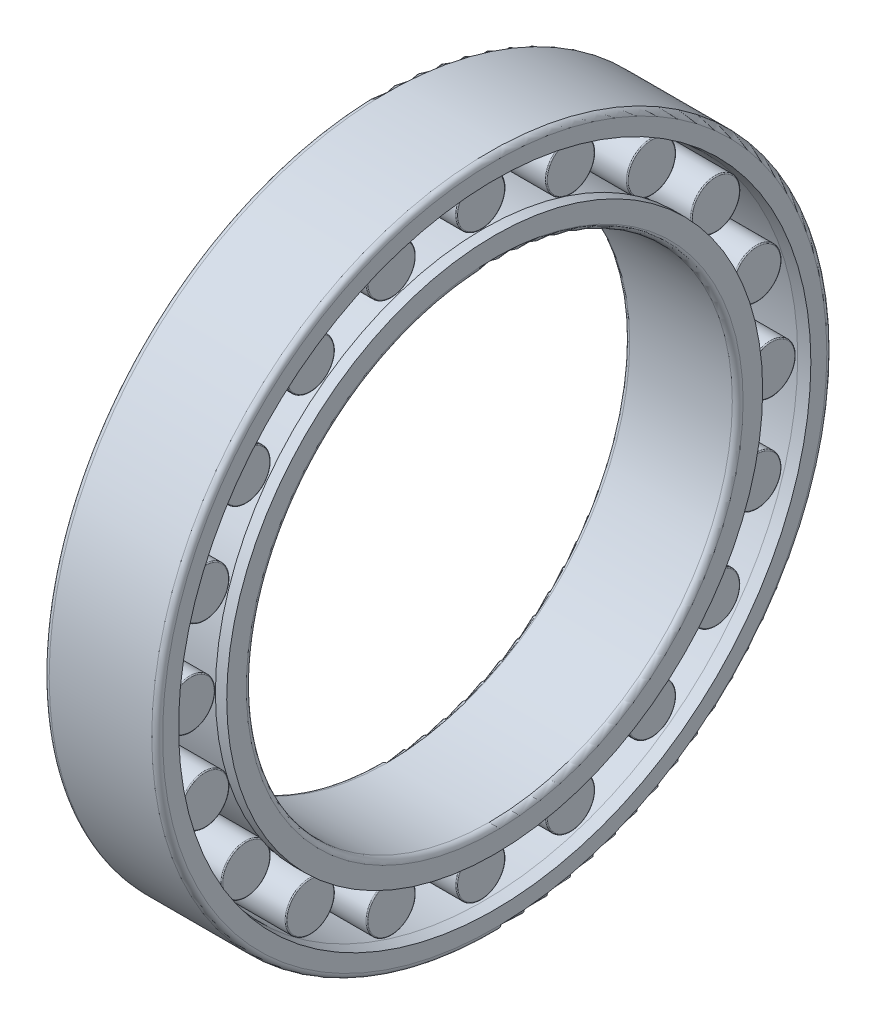
SolidWorks part; units mm, degrees
ref_plane "Plane1" through (0, 0, 0) normal (0, 0, 1) x (1, 0, 0)
ref_plane "Plane2" through (0, 0, 0) normal (0, 1, 0) x (1, 0, 0)
ref_plane "Plane3" through (0, 0, 0) normal (1, 0, 0) x (0, 0, -1)
sketch "Clipboard" plane through (0, 0, 0) normal (0, 0, 1) x (1, 0, 0)
  line L0 (-10, 0) -> (10, 0) construction
  line L1 (0, 0) -> (185.2698, -67.4327)
  line L2 (0, 0) -> (101.017, 36.7672)
  line L3 (0, 0) -> (218.798, -79.636)
  line L4 (0, 0) -> (-22.3471, -0.7804)
  dimension "Race_OD" = 232.84
  dimension "Race_ID" = 197.16
sketch "OutRacSke" plane through (0, 0, 0) normal (0, 0, 1) x (1, 0, 0)
  line L0 (16.8, 116.42) -> (21, 117.0867)
  line L1 (-21, 117.0867) -> (-21, 123)
  line L2 (-19, 125) -> (19, 125)
  line L3 (21, 123) -> (21, 117.0867)
  line L4 (-16.8, 116.42) -> (-21, 117.0867)
  line L6 (16.8, 116.42) -> (-16.8, 116.42)
  line L8 (-90, 0) -> (90, 0) construction
  arc A0 (-21, 123) -> (-19, 125) centre (-19, 123) cw
  arc A1 (19, 125) -> (21, 123) centre (19, 123) cw
  dimension "Race_OD" = 232.84
  dimension "groove_dp" = 0.6667
  dimension "halfCylLen" = 16.8
  dimension "radius" = 2
  dimension "halfWidth" = 21
  dimension "Cyl_Len" = 33.6
revolve "OuterRace" add sketch "OutRacSke" angle 360 about L8 reverse direction yes
sketch "RolDetSke" plane through (0, 0, 0) normal (0, 0, 1) x (1, 0, 0)
  line L0 (-15.96, 116.1851) -> (-15.96, 107.5)
  line L1 (-15.96, 107.5) -> (15.96, 107.5)
  line L2 (15.96, 107.5) -> (15.96, 116.1851)
  line L3 (15.5981, 116.547) -> (-15.5981, 116.547)
  line L4 (-33.6, 107.5) -> (33.6, 107.5) construction
  arc A0 (15.96, 116.1851) -> (15.5981, 116.547) centre (15.5981, 116.1851) ccw
  arc A1 (-15.5981, 116.547) -> (-15.96, 116.1851) centre (-15.5981, 116.1851) ccw
  dimension "radius" = 0.3619
  dimension "Roller_diameter" = 18.094
  dimension "halfLength" = 15.96
revolve "RollerDetailed" add sketch "RolDetSke" angle 360 about L4 reverse direction yes
ref_axis "Axis1" through (-50, 0, 0) along (1, 0, 0)
sketch "RolSimSke" plane through (0, 101.6, 0) normal (0, 0, 1) x (1, 0, 0)
  line L0 (-15.96, 14.5851) -> (-15.96, -2.7851)
  line L1 (25.4, -101.6) -> (-25.4, -101.6) construction
  line L2 (15.96, -2.7851) -> (15.96, 14.5851)
  line L3 (15.5981, 14.947) -> (-15.5981, 14.947)
  line L5 (15.5981, -3.147) -> (-15.5981, -3.147)
  arc A0 (15.96, 14.5851) -> (15.5981, 14.947) centre (15.5981, 14.5851) ccw
  arc A1 (-15.5981, 14.947) -> (-15.96, 14.5851) centre (-15.5981, 14.5851) ccw
  arc A2 (15.96, -2.7851) -> (15.5981, -3.147) centre (15.5981, -2.7851) cw
  arc A3 (-15.5981, -3.147) -> (-15.96, -2.7851) centre (-15.5981, -2.7851) cw
  dimension "radius" = 0.3619
  dimension "D1" = 98.453
  dimension "Roller_diameter" = 18.094
  dimension "halfLength" = 15.96
revolve "RollersSimplified" [suppressed] add sketch "RolSimSke" angle 360 about L1
sketch "InsRacSke" plane through (0, 0, 0) normal (0, 0, 1) x (1, 0, 0)
  line L0 (16.8, 98.58) -> (16.8, 99.2467)
  line L1 (-21, 99.2467) -> (-21, 92)
  line L2 (-19, 90) -> (19, 90)
  line L3 (21, 92) -> (21, 99.2467)
  line L4 (16.8, 99.2467) -> (21, 99.2467)
  line L5 (16.8, 98.58) -> (-16.8, 98.58)
  line L6 (-90, 0) -> (90, 0) construction
  line L8 (-16.8, 98.58) -> (-16.8, 99.2467)
  line L9 (-16.8, 99.2467) -> (-21, 99.2467)
  arc A0 (-21, 92) -> (-19, 90) centre (-19, 92) ccw
  arc A1 (19, 90) -> (21, 92) centre (19, 92) ccw
  dimension "groove_dp" = 0.6667
  dimension "halfCylLen" = 16.8
  dimension "radius" = 2
  dimension "Race_ID" = 197.16
  dimension "Width" = 42
  dimension "halfWidth" = 21
  dimension "Cyl_Len" = 33.6
revolve "InnerRace" add sketch "InsRacSke" angle 360 about L6 reverse direction yes
pattern_circular "RollersDetailed" count 20 every 18 about axis through (-50, 0, 0) along (1, 0, 0) of "RollerDetailed"
sketch "CagSpiSke" plane through (0, 0, 0) normal (0, 0, 1) x (1, 0, 0)
  line L0 (18.9, 105.2383) -> (18.9, 109.7618)
  line L1 (18.9, 109.7618) -> (-18.9, 109.7618)
  line L2 (-18.9, 109.7618) -> (-18.9, 105.2383)
  line L3 (-18.9, 105.2383) -> (18.9, 105.2383)
  line L4 (-90, 0) -> (90, 0) construction
revolve "CageSpine" [suppressed] add sketch "CagSpiSke" angle 360 about L4
equation "\"CLdia@Clipboard\" =  ( \"Race_OD@Clipboard\" + \"Race_ID@Clipboard\" )  / 4"
equation "\"Race_OD@OutRacSke\" = \"Race_OD@Clipboard\""
equation "\"halfCylLen@OutRacSke\" = \"Cyl_Len@OutRacSke\" / 2"
equation "\"groove_dp@OutRacSke\" = \"radius@OutRacSke\" / 3"
equation "\"RolCLRad@RolDetSke\" = \"CLdia@Clipboard\""
equation "\"Roller_diameter@RolDetSke\" =  ( \"Race_OD@Clipboard\" - \"Race_ID@Clipboard\" )  / 2 + .01"
equation "\"Roller_diameter@RolSimSke\" =  ( \"Race_OD@Clipboard\" - \"Race_ID@Clipboard\" )  / 2 + .01"
equation "\"radius@RolDetSke\" = \"Roller_diameter@RolDetSke\" / 50"
equation "\"Length@RolDetSke\" = \"Cyl_Len@OutRacSke\" * .95"
equation "\"halfLength@RolDetSke\" = \"Length@RolDetSke\" / 2"
equation "\"thickness@CagSpiSke\"  = \"Roller_diameter@RolDetSke\" * .25"
equation "\"Cag_IR@CagSpiSke\" =  \"RolCLRad@RolDetSke\" * 2 - \"thickness@CagSpiSke\""
equation "\"Rol_Length@RolSimSke\" = \"Cyl_Len@InsRacSke\" * .95"
equation "\"halfLength@RolSimSke\" = \"Rol_Length@RolSimSke\" / 2"
equation "\"radius@RolSimSke\" = \"radius@RolDetSke\""
equation "\"D1@RolSimSke\" = \"CLdia@Clipboard\" -  ( \"Roller_diameter@RolSimSke\" / 2 ) "
equation "\"Max_count@Clipboard\" = int( 3.14159265 / atn(( \"Roller_diameter@RolDetSke\" / 2) / sqr( \"RolCLRad@RolDetSke\"  *  \"RolCLRad@RolDetSke\" - ( \"Roller_diameter@RolDetSke\" / 2) *  ( \"Roller_diameter@RolDetSke\" / 2))))"
equation "\"Max_count@Clipboard\" = ((sgn( \"Max_count@Clipboard\" - \"Count@Clipboard\" )-1)*( \"Max_count@Clipboard\" - \"Count@Clipboard\" ))/-2+ \"Count@Clipboard\""
equation "\"Count@RollersDetailed\" = int( \"Show_count@Clipboard\" ) "
equation "\"Count@RollersDetailed\" = ((sgn( \"Count@RollersDetailed\" - \"Max_count@Clipboard\" )-1)*( \"Count@RollersDetailed\" - \"Max_count@Clipboard\" ))/-2+ \"Max_count@Clipboard\""
equation "\"Count@RollersDetailed\" = ((sgn( \"Count@RollersDetailed\" - \"Min_count@Clipboard\" )+1)*( \"Count@RollersDetailed\" - \"Min_count@Clipboard\"))/2 +\"Min_count@Clipboard\""
equation "\"Angle@RollersDetailed\" = 360.0 / \"Max_count@Clipboard\""
equation "\"radius@InsRacSke\" = \"radius@OutRacSke\""
equation "\"Width@InsRacSke\" = \"Width@OutRacSke\""
equation "\"halfWidth@OutRacSke\" = \"Width@OutRacSke\" / 2"
equation "\"halfWidth@InsRacSke\" = \"Width@InsRacSke\" / 2"
equation "\"Race_ID@InsRacSke\" = \"Race_ID@Clipboard\""
equation "\"Cyl_Len@InsRacSke\" = \"Cyl_Len@OutRacSke\""
equation "\"halfCylLen@InsRacSke\" = \"Cyl_Len@InsRacSke\" / 2"
equation "\"Angle@CageSpine\" =  \"Angle@RollersDetailed\" * ( \"Count@RollersDetailed\" -1 + int( \"Count@RollersDetailed\" / \"Max_count@Clipboard\" ) )  + 0.001 -  int( \"Count@RollersDetailed\" / \"Max_count@Clipboard\" ) * 0.001"
equation "\"Angle@CageSpine\" =  \"Angle@CageSpine\" * int( \"Min_count@Clipboard\" / 2) + int(1 / \"Min_count@Clipboard\")  * 0.001"
equation "\"width@CagSpiSke\" =   ( \"Width@InsRacSke\" + \"Cyl_Len@InsRacSke\" )  / 2"
equation "\"halfwidth@CagSpiSke\" = \"width@CagSpiSke\" / 2"
